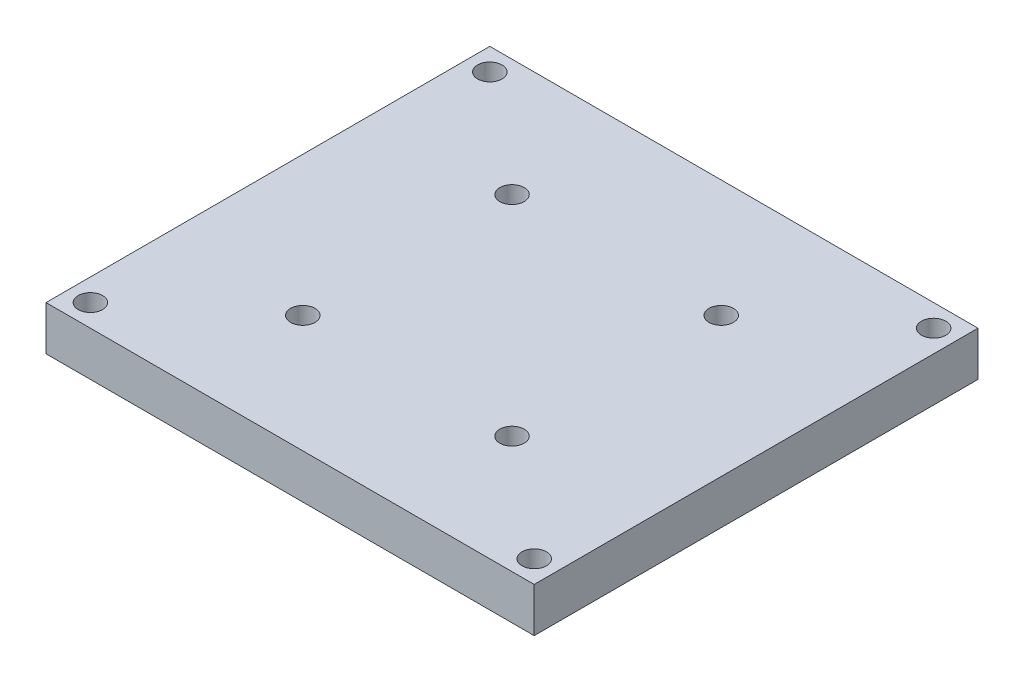
SolidWorks part; units mm, degrees
ref_plane "Front Plane" through (0, 0, 0) normal (0, 0, 1) x (1, 0, 0)
ref_plane "Top Plane" through (0, 0, 0) normal (0, 1, 0) x (1, 0, 0)
ref_plane "Right Plane" through (0, 0, 0) normal (1, 0, 0) x (0, 0, -1)
sketch "Sketch2" plane through (0, 0, 0) normal (0, 1, 0) x (1, 0, 0)
  line L1 (0, 0) -> (47.14, 0)
  line L2 (0, 0) -> (0, 47.14)
  line L3 (0, 47.14) -> (47.14, 47.14)
  line L4 (47.14, 0) -> (47.14, 47.14)
  line L5 (-26.43, 68.57) -> (73.57, 68.57)
  line L6 (-26.43, 68.57) -> (-26.43, -21.43)
  line L7 (-26.43, -21.43) -> (73.57, -21.43)
  line L8 (73.57, 68.57) -> (73.57, -21.43)
  line L9 (-31.43, 73.57) -> (78.57, 73.57)
  line L10 (-31.43, 73.57) -> (-31.43, -26.43)
  line L11 (-31.43, -26.43) -> (78.57, -26.43)
  line L12 (78.57, 73.57) -> (78.57, -26.43)
  circle A0 centre (0, 47.14) radius 2.75
  circle A1 centre (47.14, 47.14) radius 2.75
  circle A2 centre (47.14, 0) radius 2.75
  circle A3 centre (0, 0) radius 2.75
  circle A4 centre (-26.43, 68.57) radius 2.75
  circle A5 centre (73.57, 68.57) radius 2.75
  circle A6 centre (73.57, -21.43) radius 2.75
  circle A7 centre (-26.43, -21.43) radius 2.75
  dimension "D3" = 100
  dimension "D7" = 110
  dimension "D1" = 47.14
  dimension "D2" = 47.14
  dimension "D4" = 90
  dimension "D5" = 21.43
  dimension "D6" = 26.43
  dimension "D8" = 100
  dimension "D9" = 5
  dimension "D10" = 5
extrude "Boss-Extrude1" add sketch "Sketch2" along normal blind 10 contours L12 L9 L10 L11 A7 L6 A4 L5 A5 L8 A6 L7 | A7 L7 A6 L8 A5 L5 A4 L6 A3 L2 A0 L3 A1 L4 A2 L1 | A3 L1 A2 L4 A1 L3 A0 L2 region at (23.57, 0, -23.57) region at (23.57, 0, -67.2246) region at (23.57, 0, -72.0834)
